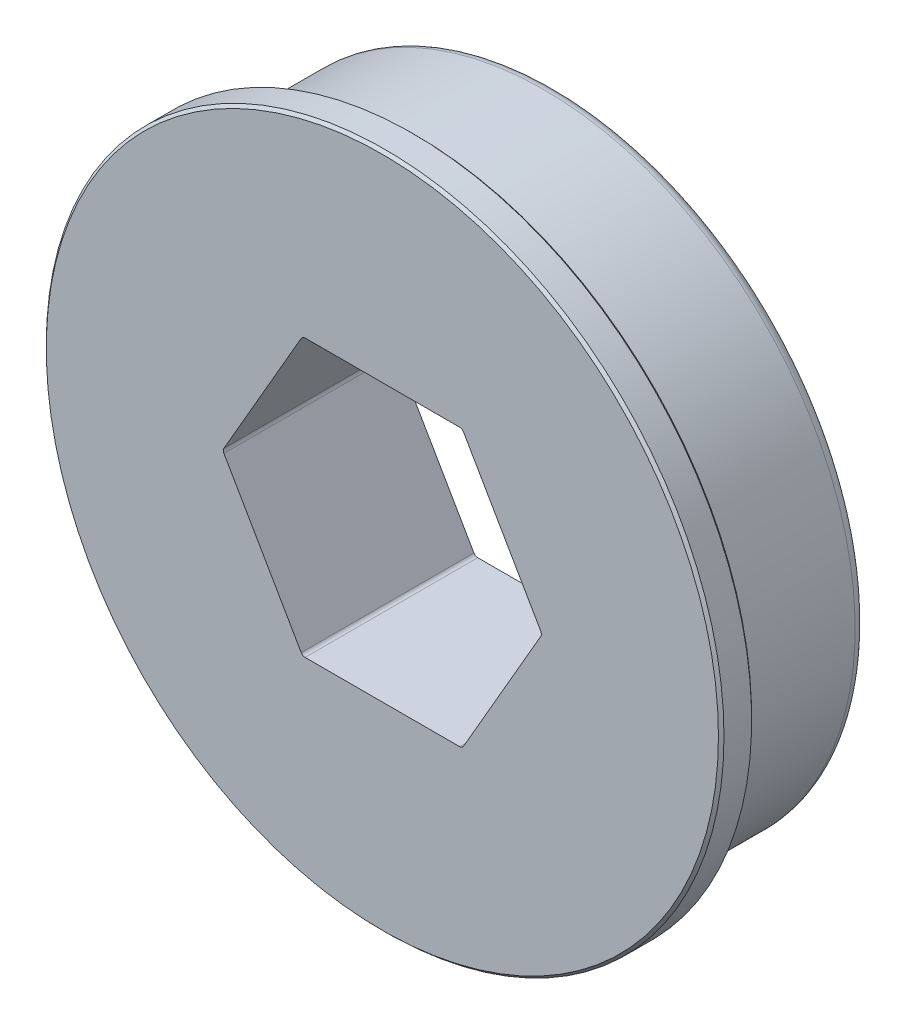
SolidWorks part; units mm, degrees
material "1023 Carbon Steel Sheet (SS)"
ref_plane "Front Plane" through (0, 0, 0) normal (0, 0, 1) x (1, 0, 0)
ref_plane "Top Plane" through (0, 0, 0) normal (0, 1, 0) x (1, 0, 0)
ref_plane "Right Plane" through (0, 0, 0) normal (1, 0, 0) x (0, 0, -1)
ref_plane "Plane1" through (0, 0, 0) normal (0, -1, 0) x (1, 0, 0)
sketch "Sketch1" plane through (0, 0, 0) normal (0, -1, 0) x (1, 0, 0)
  line L0 (15.5575, 7.9273) -> (0, 7.9273)
  line L1 (0, 7.9273) -> (0, 0)
  line L2 (0, 0) -> (14.2875, 0)
  line L3 (14.2875, 0) -> (14.2875, 5.8953)
  line L4 (14.2875, 5.8953) -> (13.97, 5.8953)
  line L5 (13.97, 5.8953) -> (13.97, 6.4033)
  line L6 (13.97, 6.4033) -> (15.5575, 6.4033)
  line L7 (15.5575, 6.4033) -> (15.5575, 7.9273)
  line L8 (0, 7.9273) -> (0, 0) construction
revolve "Revolve1" add sketch "Sketch1" angle 360 about L8 reverse direction yes
sketch "Sketch2" plane through (0, 0, 0) normal (0, 0, -1) x (-1, 0, 0)
  line L0 (3.6662, 6.35) -> (-3.6662, 6.35)
  line L1 (-3.6662, 6.35) -> (-7.3323, 0)
  line L2 (-7.3323, 0) -> (-3.6662, -6.35)
  line L3 (-3.6662, -6.35) -> (3.6662, -6.35)
  line L4 (3.6662, -6.35) -> (7.3323, 0)
  line L5 (7.3323, 0) -> (3.6662, 6.35)
  line L6 (3.6662, 6.35) -> (-3.6662, -6.35) construction
  line L8 (-3.8862, -6.7311) -> (-3.6662, -6.35) construction
  circle A0 centre (0, 0) radius 6.35 construction
  circle A1 centre (0, 0) radius 7.7724 construction
  dimension "D1" = 12.7
  dimension "D2" = 15.5448
  dimension "D3" = 0.4401
extrude "Cut-Extrude1" cut sketch "Sketch2" against normal through all
chamfer "Chamfer1" distance 0.127 angle 45 1 edges at (-15.5575, 0, 6.4033)
chamfer "Chamfer2" distance 0.127 angle 45 1 edges at (-15.5575, 0, 7.9273)
fillet "Fillet1" radius 0.508 1 edges at (-14.2875, 0, 0) tangent propagation no
fillet "Fillet2" radius 0.2032 6 edges at (3.6662, 6.35, 3.9637) (7.3323, 0, 3.9637) (3.6662, -6.35, 3.9637) (-3.6662, -6.35, 3.9637) (-7.3323, 0, 3.9637) (-3.6662, 6.35, 3.9637)
